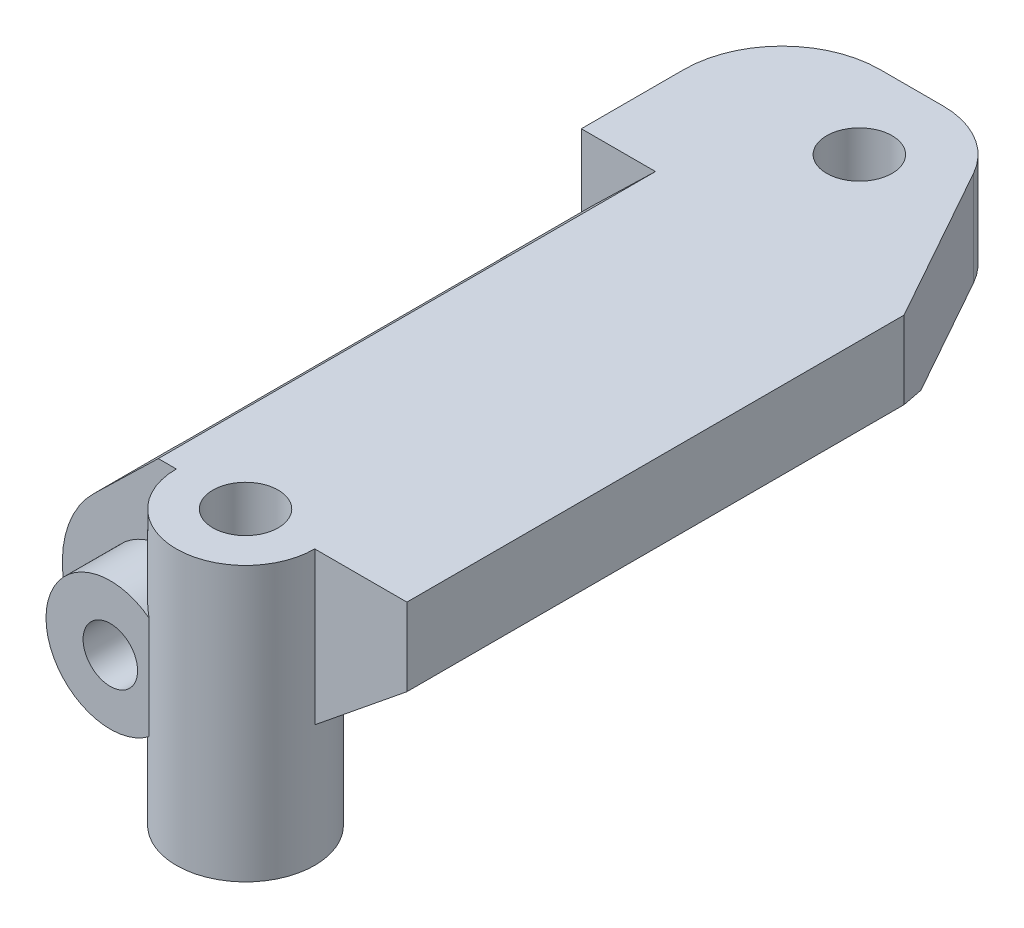
SolidWorks part; units mm, degrees
ref_plane "Front Plane" through (0, 0, 0) normal (0, 0, 1) x (1, 0, 0)
ref_plane "Top Plane" through (0, 0, 0) normal (0, 1, 0) x (1, 0, 0)
ref_plane "Right Plane" through (0, 0, 0) normal (1, 0, 0) x (0, 0, -1)
sketch "Sketch2" plane through (0, 0, 0) normal (0, 1, 0) x (1, 0, 0)
  line L0 (-5.7, 6.8) -> (-9.1, 6.8)
  line L1 (-5.7, -16) -> (5.7, -16)
  line L2 (-5.7, -16) -> (-5.7, 16)
  line L3 (-5.7, 16) -> (5.7, 16)
  line L4 (5.7, -16) -> (5.7, 16)
  line L5 (-5.7, -16) -> (5.7, 16) construction
  line L6 (-5.7, 16) -> (5.7, -16) construction
  line L7 (-9.1, 6.8) -> (-9.1, 11.5)
  line L8 (-4.6, 16) -> (-5.7, 16)
  line L9 (5.7, 6.8) -> (1.6608, 14.0281)
  arc A0 (-9.1, 11.5) -> (-4.6, 16) centre (-4.6, 11.5) cw
  arc A1 (1.6608, 14.0281) -> (-1.7, 16) centre (-1.7, 12.15) ccw
  circle A2 centre (-1.7, -16) radius 3.175
  point P0 (0, 0)
  point P12 (0, 0)
  point P14 (0, 0)
  point P19 (-2.2237, -16)
  point P20 (0, 0)
  dimension "D1" = 4.5
  dimension "D7" = 6.35
  dimension "D2" = 32
  dimension "D3" = 11.4
  dimension "D4" = 14.8
  dimension "D5" = 9.2
  dimension "D6" = 28.15
  dimension "D8" = 7.4
extrude "Boss-Extrude1" add sketch "Sketch2" along normal blind 4.35 contours L1 A2 | A2 L1 L4 L9 A1 L3 A0 L2 | L1 A2 | A0 L7 L0 L2 region at (-0.2076, 0, 0.27) region at (-7.2845, 0, -10.8295) region at (-1.7, 0, 14.6525) region at (-1.7, 0, 17.3475)
sketch "Sketch3" plane through (0, 0, 16) normal (0, 0, 1) x (1, 0, 0)
  line L0 (-5.7, 4.35) -> (-8.6425, 1.4949)
  line L1 (5.7, 0.79) -> (-2.2768, -5.6783)
  line L2 (5.7, 4.35) -> (5.7, 0) construction
  line L3 (1.475, 4.35) -> (5.7, 4.35) construction
  line L4 (1.475, 4.35) -> (-4.875, 4.35) construction
  line L5 (-5.7, 4.35) -> (5.7, 0.79)
  circle A0 centre (-5.3, -1.95) radius 4.8
  point P15 (-10.1, -1.95)
  line M4 (-5.7, 0) -> (-4.875, 0)
  line M5 (-4.875, 0) -> (-4.875, 4.35)
  line M7 (-5.7, 4.35) -> (-5.7, 0)
  dimension "D3" = 9.6
  dimension "D1" = 3.56
  dimension "D2" = 15.8
  dimension "D4" = 6.3
extrude "Boss-Extrude2" add sketch "Sketch3" against normal up to surface (22.8 mm away) contours A0 L1 L5 M5 | A0 M7 M5 M4 | A0 M5 M7 M4 | A0 L5 M5 M7 | A0 L0 M7 region at (-6.4799, 3.1271, 16) region at (-5.3003, 3.5346, 16) region at (-5.3004, -2.063, 16) region at (0.5611, 0.2898, 16) region at (-5.2876, 1.422, 16) up to face at (-7.4, 2.175, -6.8)
sketch "Sketch4" plane through (0, 0, 16) normal (0, 0, 1) x (1, 0, 0)
  line L0 (4.7258, 0) -> (-2.2768, -5.6783) construction
  line L1 (4.7258, 0) -> (5.7, 0) construction
  line L2 (5.7, 4.35) -> (5.7, 0) construction
  line L3 (5.7, 0.79) -> (4.7258, 0)
  line L4 (4.7258, 0) -> (5.7, 0)
  line L5 (5.7, 0.79) -> (5.7, 0)
  line M10 (4.7258, 0) -> (5.7, 0)
  line M11 (5.7, 0) -> (5.7, 4.35)
extrude "Cut-Extrude1" cut sketch "Sketch4" against normal through all contours L3 M11 M10 region at (5.3753, 0.2633, 16)
sketch "Sketch5" plane through (0, 4.35, 0) normal (0, 1, 0) x (1, 0, 0)
  circle A0 centre (-1.7, -16) radius 3.175
extrude "Boss-Extrude3" add sketch "Sketch5" against normal blind 12.57
sketch "Sketch6" plane through (0, 0, 16) normal (0, 0, 1) x (1, 0, 0)
  circle A0 centre (-5.3, -1.95) radius 2.95
  dimension "D1" = 5.9
extrude "Boss-Extrude4" add sketch "Sketch6" along normal offset from surface (2.6 mm away) 25.4 up to face at (-4.6789, -1.9331, -6.8)
chamfer "Chamfer1" distance 1.5 angle 45 1 edges at (1.2245, -2.8391, -6.8) tangent propagation no
sketch "Sketch7" plane through (0, 4.35, 0) normal (0, 1, 0) x (1, 0, 0)
  circle A0 centre (-1.7, 12.15) radius 1.5
  circle A1 centre (-1.7, -16) radius 1.5
  dimension "D1" = 3
extrude "Cut-Extrude2" cut sketch "Sketch7" against normal through all
sketch "Sketch8" plane through (0, 0, 18.6) normal (0, 0, 1) x (1, 0, 0)
  circle A0 centre (-5.3, -1.95) radius 1.25
  dimension "D1" = 2.5
extrude "Cut-Extrude3" cut sketch "Sketch8" against normal through all
ref_plane "Plane1" through (3.7, 0, 0) normal (1, 0, 0) x (0, 0, -1)
sketch "Sketch9" plane through (3.7, 0, 0) normal (1, 0, 0) x (0, 0, -1)
  line L0 (-16, -6.75) -> (6.3717, -6.75) construction
  line L1 (-12.3141, 1.85) -> (2.6859, 1.85)
  line L2 (-12.3141, 1.85) -> (-12.3141, -6.75)
  line L3 (-12.3141, -6.75) -> (2.6859, -6.75)
  line L4 (2.6859, 1.85) -> (2.6859, -6.75)
  line L5 (-12.3141, 1.85) -> (2.6859, -6.75) construction
  line L6 (-12.3141, -6.75) -> (2.6859, 1.85) construction
  line L7 (-16, 4.35) -> (6.8, 4.35) construction
  point P0 (-4.8141, -2.45)
  point P7 (0, 0)
  point P10 (0, 0)
  point P11 (-4.8141, -6.75)
  dimension "D1" = 15
  dimension "D2" = 2.5
extrude "Cut-Extrude4" cut sketch "Sketch9" against normal blind 25.4
chamfer "Chamfer2" distance 2.5 angle 45 1 edges at (3.7, 1.85, 4.8141)
fillet "Fillet1" radius 0.25 1 edges at (3.7, -0.8318, 4.8141)
ref_plane "Plane2" through (0, 0, 4.8141) normal (0, 0, 1) x (1, 0, 0)
